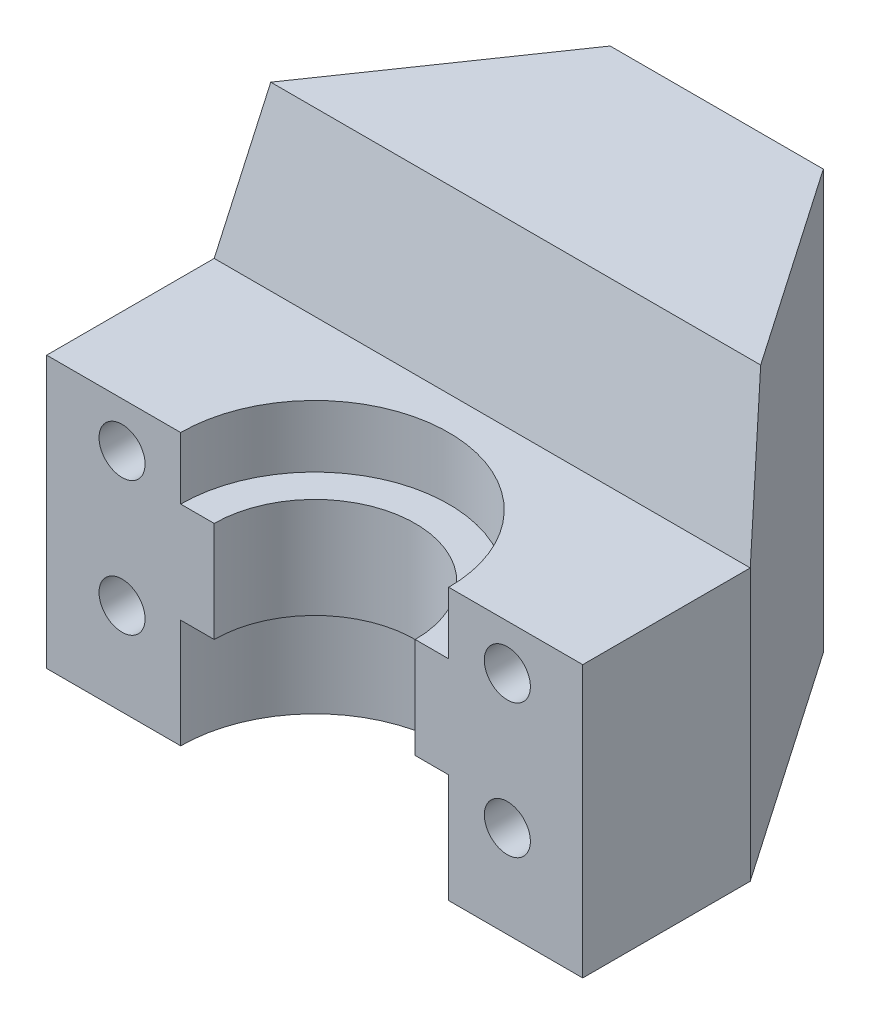
SolidWorks part; units mm, degrees
material "PLA"
ref_plane "Front Plane" through (0, 0, 0) normal (0, 0, 1) x (1, 0, 0)
ref_plane "Top Plane" through (0, 0, 0) normal (0, 1, 0) x (1, 0, 0)
ref_plane "Right Plane" through (0, 0, 0) normal (1, 0, 0) x (0, 0, -1)
sketch "Sketch1" plane through (0, 0, 0) normal (1, 0, 0) x (0, 0, -1)
  line L0 (0, 20) -> (12, 20) construction
  line L1 (0, 0) -> (12, 0)
  line L2 (0, 0) -> (0, 25)
  line L3 (0, 25) -> (12, 25)
  line L4 (12, 0) -> (12, 25)
  line L5 (0, 5) -> (12, 5) construction
  dimension "D1" = 15
  dimension "D2" = 12
  dimension "D3" = 25
  dimension "D4" = 5
extrude "Boss-Extrude1" add sketch "Sketch1" along normal mid plane 32 contours L4 L3 L2 L1
sketch "Sketch2" plane through (0, 0, 0) normal (0, 1, 0) x (1, 0, 0)
  line L0 (0, 0) -> (0, -2) construction
  line L1 (-16, -12) -> (16, -12)
  line L2 (-16, -12) -> (-16, -2)
  line L3 (-16, -2) -> (16, -2)
  line L4 (16, -12) -> (16, -2)
  line L5 (16, 0) -> (16, 12) construction
  dimension "D1" = 2
  dimension "D3" = 10
extrude "Boss-Extrude2" add sketch "Sketch2" along normal blind 16.2 separate body
sketch "Sketch3" plane through (16, 0, 0) normal (1, 0, 0) x (0, 0, -1)
  line L1 (-2, 0) -> (-2, 16.2) construction
  line L7 (0, 25) -> (0, 0) construction
  line L9 (-2, 0) -> (-2, 16.2)
  line L15 (0, 25) -> (0, 0)
  line L16 (0, 25) -> (-2, 16.2)
  line L17 (-2, 0) -> (0, 0)
extrude "Boss-Extrude3" add sketch "Sketch3" against normal up to surface (32 mm away) up to face at (-16, 8.1, 7)
hole_wizard "M5x0.8 Tapped Hole1" positions "Sketch7" profile "Sketch6" tap size "M5x0.8" standard "ANSI Metric"
sketch "Sketch7" plane through (0, 0, -12) normal (0, 0, -1) x (-1, 0, 0)
  line L0 (-16, 0) -> (16, 0) construction
  point P0 (0, 20)
  point P2 (0, 5)
  dimension "D1" = 15
  dimension "D2" = 5
sketch "Sketch6" plane through (0, 20, -12) normal (1, 0, 0) x (0, 1, 0)
  line L0 (0, 0) -> (0, 10.2618)
  line L1 (0, 10.2618) -> (2.1, 9)
  line L2 (2.1, 9) -> (2.1, 0)
  line L5 (2.1, 0) -> (0, 0)
  line L10 (0, 10.2618) -> (-2.1, 9) construction
  line L11 (0, -6.35) -> (0, 107.95) construction
  dimension "Tap Drill Dia." = 4.2
  dimension "Tap Drill Depth" = 9
  dimension "Drill Angle" = 118
cosmetic thread "Hole Thread1" parameters "D1"=4.2, "D2"=5
cosmetic thread "Hole Thread2" parameters "D1"=4.2, "D2"=5
sketch "Sketch9" plane through (0, 0, 0) normal (1, 0, 0) x (0, 0, -1)
  line L0 (-12, 16.2) -> (-4, 16.2)
  line L1 (-12, 16.2) -> (-12, 0) construction
  line L2 (-4, 16.2) -> (-4, 12.5)
  line L3 (-4, 12.5) -> (-6, 12.5)
  line L4 (-6, 12.5) -> (-6, 6.5)
  line L5 (-6, 6.5) -> (-4, 6.5)
  line L6 (-4, 6.5) -> (-4, 0)
  line L7 (-12, 0) -> (12, 0) construction
  line L8 (-4, 0) -> (-12, 0)
  line L9 (-12, 0) -> (-12, 16.2)
  line L10 (-12, 16.2) -> (-2, 16.2) construction
  dimension "D1" = 6
  dimension "D2" = 8
  dimension "D3" = 8
  dimension "D4" = 6.5
  dimension "D5" = 6
revolve "Cut-Revolve1" cut sketch "Sketch9" angle 360 about L9
sketch "Sketch10" plane through (0, 25, 0) normal (0, 1, 0) x (1, 0, 0)
  line L5 (16, -2) -> (16, 0) construction
  line L6 (-16, -2) -> (-6.3625, 12)
  line L7 (16, 12) -> (-16, 12) construction
  line L8 (-6.3625, 12) -> (-16, 12)
  line L9 (-16, 12) -> (-16, -2)
  line L10 (16, 12) -> (6.3625, 12)
  line L11 (16, -2) -> (16, 0)
  line L12 (6.3625, 12) -> (16, -2)
  line L13 (16, 12) -> (16, -2)
  line L14 (0, 0) -> (0, 12) construction
  line L15 (16, 0) -> (-16, 0) construction
  line M4 (-16, 12) -> (-16, 0)
  line M5 (-16, 0) -> (16, 0)
  line M6 (16, 0) -> (16, 12)
  line M7 (16, 12) -> (-16, 12)
  dimension "D1" = 12.725
extrude "Cut-Extrude2" cut sketch "Sketch10" against normal up to next contours L12 M7 M5 M6 | L12 L11 M5 | L6 M5 M7 M4 | L9 L6 M5 region at (-15.5411, 25, 0.6667) region at (-12.7301, 25, -7.5) region at (15.5411, 25, 0.6667) region at (12.7301, 25, -7.5)
hole_wizard "M3x0.5 Tapped Hole1" positions "Sketch12" profile "Sketch11" tap size "M3x0.5" standard "ANSI Metric"
sketch "Sketch12" plane through (0, 0, 12) normal (0, 0, 1) x (1, 0, 0)
  line L0 (0, 0) -> (0, 16.2) construction
  line L1 (8, 16.2) -> (-8, 16.2) construction
  line L4 (-11.5, 13.5) -> (-11.5, 5.5) construction
  line L7 (-11.5, 9.5) -> (0, 9.5) construction
  line L10 (-6, 6.5) -> (-6, 12.5) construction
  point P0 (-11.5, 13.5)
  point P2 (11.5, 13.5)
  point P7 (-11.5, 5.5)
  point P8 (11.5, 5.5)
  point P36 (-6, 9.5)
  dimension "D1" = 8
  dimension "D2" = 23
sketch "Sketch11" plane through (-11.5, 13.5, 12) normal (1, 0, 0) x (0, -1, 0)
  line L0 (0, 0) -> (0, 12.8262)
  line L1 (0, 12.8262) -> (1.375, 12)
  line L2 (1.375, 12) -> (1.375, 0)
  line L5 (1.375, 0) -> (0, 0)
  line L10 (0, 12.8262) -> (-1.375, 12) construction
  line L11 (0, -6.35) -> (0, 107.95) construction
  dimension "Tap Drill Dia." = 2.75
  dimension "Tap Drill Depth" = 12
  dimension "Drill Angle" = 118
cosmetic thread "Hole Thread3" parameters "D1"=6, "D2"=3
cosmetic thread "Hole Thread4" parameters "D1"=6, "D2"=3
cosmetic thread "Hole Thread5" parameters "D1"=6, "D2"=3
cosmetic thread "Hole Thread6" parameters "D1"=6, "D2"=3
